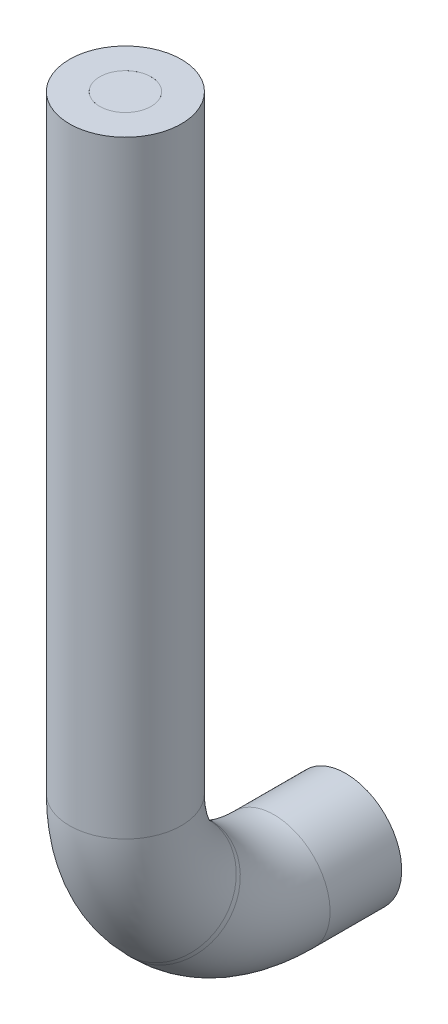
SolidWorks part; units mm, degrees
ref_plane "Спереди" through (0, 0, 0) normal (0, 0, 1) x (1, 0, 0)
ref_plane "Сверху" through (0, 0, 0) normal (0, 1, 0) x (1, 0, 0)
ref_plane "Справа" through (0, 0, 0) normal (1, 0, 0) x (0, 0, -1)
sketch "Эскиз1" plane through (0, 0, 0) normal (1, 0, 0) x (0, 0, -1)
  line L0 (0, 0) -> (-50000, 0) construction
  line L1 (0, 0) -> (0, -50000) construction
  line L2 (0, 11.5) -> (0, 2.2613)
  line L3 (0.6444, 0.7056) -> (0.7056, 0.6444)
  line L4 (2.2613, 0) -> (3.35, 0)
  arc A0 (0.7056, 0.6444) -> (2.2613, 0) centre (2.2613, 2.2) ccw
  arc A1 (0, 2.2613) -> (0.6444, 0.7056) centre (2.2, 2.2613) ccw
  point P11 (1.35, 0)
  point P14 (0, 1.35)
  dimension "D2" = 2.2
  dimension "D1" = 45
  dimension "D3" = 9.2387
  dimension "D4" = 2.2613
  dimension "D5" = 3.35
ref_plane "Плоскость1" through (0, 0, -3.35) normal (0, 0, 1) x (1, 0, 0)
sketch "Эскиз2" plane through (0, 0, -3.35) normal (0, 0, 1) x (1, 0, 0)
  circle A0 centre (0, 0) radius 0.39
  dimension "D1" = 0.78
sweep "По траектории1" add profiles "Эскиз2" path "Эскиз1"
sketch "Эскиз3" plane through (0, 0, -3.35) normal (0, 0, -1) x (-1, 0, 0)
  circle A0 centre (0, 0) radius 0.39 construction
  circle A1 centre (0, 0) radius 0.39
  circle A2 centre (0, 0) radius 0.85
  dimension "D1" = 1.7
sweep "По траектории2" add profiles "Эскиз3" path "Эскиз1<2>"
sketch "Эскиз1<2>" plane through (0, 0, 0) normal (1, 0, 0) x (0, 0, -1) same geometry as "Эскиз1"
